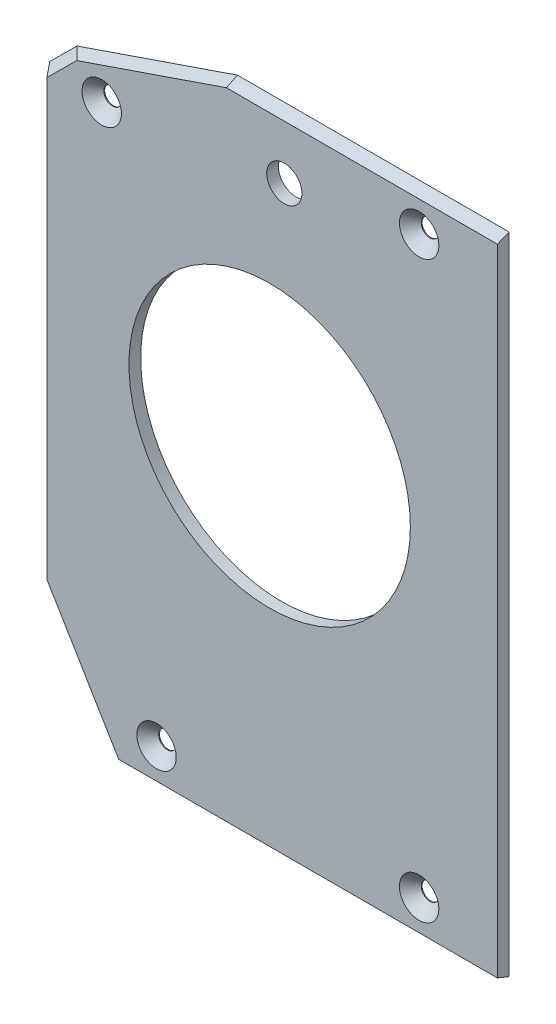
SolidWorks part; units mm, degrees
ref_plane "Front Plane" through (0, 0, 0) normal (0, 0, 1) x (1, 0, 0)
ref_plane "Top Plane" through (0, 0, 0) normal (0, 1, 0) x (1, 0, 0)
ref_plane "Right Plane" through (0, 0, 0) normal (1, 0, 0) x (0, 0, -1)
sketch "Sketch1" plane through (0, 0, 0) normal (0, 0, 1) x (1, 0, 0)
  line L9 (38.85, -60) -> (38.85, 50)
  line L12 (-39.5, 36.014) -> (-39.5, -39.169)
  line L13 (38.85, 50) -> (-7.5, 50)
  line L14 (-7.5, 50) -> (-34.8474, 40.6238)
  line L16 (-39.5, -39.169) -> (-27.0014, -60)
  line L17 (-27.0014, -60) -> (38.85, -60)
  line L171 (-34.8474, 40.6238) -> (-39.5, 36.014)
  circle A2 centre (0, 0) radius 23
  circle A3 centre (0, 0) radius 24
extrude "Boss-Extrude1" add sketch "Sketch1" along normal blind 2 contours L16 L17 L9 L13 L14 L12 A3 region at (5.9243, -58.6495, 0)
chamfer "Chamfer1" distance 2 distance2 1.5 3 edges at (-39.5, -1.5775, 2) (-33.2507, -49.5845, 2) (-37.1737, 38.3189, 2) first distance on face at (-39.5, -1.5775, 1) first distance on face at (-33.2507, -49.5845, 1) first distance on face at (-37.1737, 38.3189, 1)
sketch "Sketch3" plane through (0, 0, 2) normal (0, 0, 1) x (1, 0, 0)
  line L0 (-42.5, -40) -> (-42.5, 33.1739) construction
  line L4 (-7.5, 50) -> (38.85, 50) construction
  circle A0 centre (2.5, 40) radius 3
  circle A1 centre (-19.2911, -54) radius 1.5 construction
  circle A2 centre (25.5, -54) radius 1.5 construction
  circle A3 centre (25.5, 44) radius 1.5 construction
  circle A4 centre (-28.6429, 36.4081) radius 1.5 construction
  circle A5 centre (-19.2911, -54) radius 1.5
  circle A6 centre (25.5, -54) radius 1.5
  circle A7 centre (25.5, 44) radius 1.5
  circle A8 centre (-28.6429, 36.4081) radius 1.5
  dimension "D1" = 45
  dimension "D3" = 6
  dimension "D2" = 10
extrude "Cut-Extrude1" cut sketch "Sketch3" against normal blind 2
chamfer "Chamfer2" distance 2 distance2 0.8 3 edges at (6.7989, -60, 2) (15.675, 50, 2) (-19.5442, 45.8706, 2) first distance on face at (6.3616, -60, 1) first distance on face at (15.675, 50, 1) first distance on face at (-20.3589, 45.5912, 1)
chamfer "Chamfer3" distance 1.86 angle 45 4 edges at (-17.7911, -54, 2) (27, -54, 2) (27, 44, 2) (-27.1429, 36.4081, 2)
